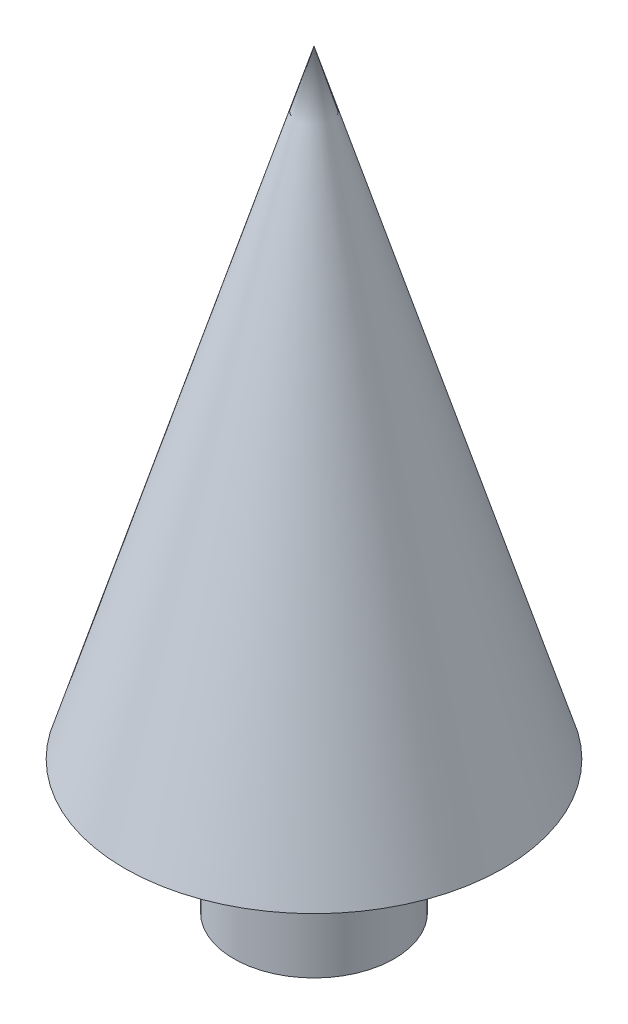
SolidWorks part; units mm, degrees
ref_plane "Front Plane" through (0, 0, 0) normal (0, 0, 1) x (1, 0, 0)
ref_plane "Top Plane" through (0, 0, 0) normal (0, 1, 0) x (1, 0, 0)
ref_plane "Right Plane" through (0, 0, 0) normal (1, 0, 0) x (0, 0, -1)
sketch "Sketch2" plane through (0, 0, 0) normal (0, 0, 1) x (1, 0, 0)
  line L0 (0, 0) -> (0, 150)
  line L1 (0, 150) -> (37.863, 26.563)
  line L2 (37.863, 26.563) -> (16.0453, 26.563)
  line L3 (16.0453, 26.563) -> (16.0453, 0)
  line L4 (16.0453, 0) -> (0, 0)
  dimension "D1" = 150
  dimension "D2" = 16.0453
  dimension "D3" = 123.437
  dimension "D4" = 21.8177
revolve "Revolve1" add sketch "Sketch2" angle 360 about L0
